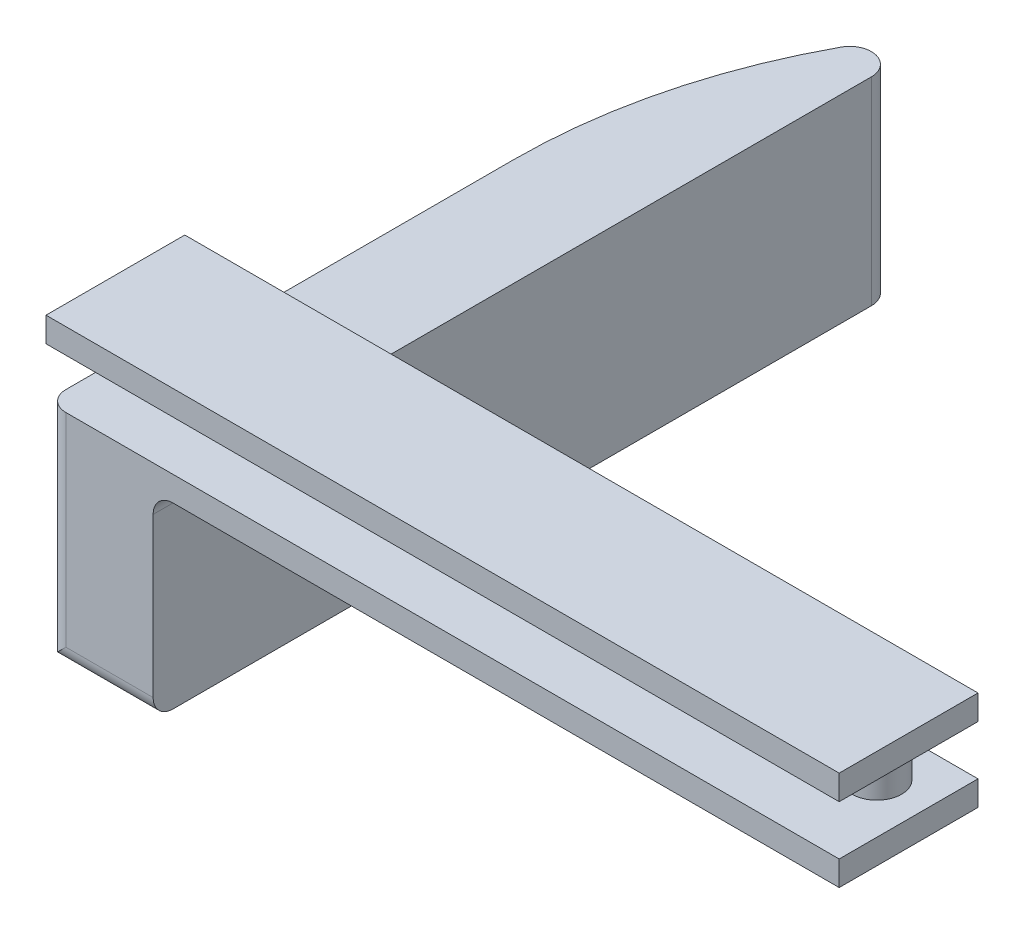
SolidWorks part; units mm, degrees
ref_plane "Front Plane" through (0, 0, 0) normal (0, 0, 1) x (1, 0, 0)
ref_plane "Top Plane" through (0, 0, 0) normal (0, 1, 0) x (1, 0, 0)
ref_plane "Right Plane" through (0, 0, 0) normal (1, 0, 0) x (0, 0, -1)
sketch "Sketch2" plane through (0, 0, 0) normal (0, 1, 0) x (1, 0, 0)
  line L1 (0, 0) -> (101.6, 0)
  line L2 (0, 0) -> (0, 17.78)
  line L3 (0, 17.78) -> (101.6, 17.78)
  line L4 (101.6, 0) -> (101.6, 17.78)
  dimension "D1" = 17.78
  dimension "D2" = 101.6
extrude "Boss-Extrude1" add sketch "Sketch2" along normal blind 3.175
sketch "Sketch3" plane through (0, 0, 0) normal (0, -1, 0) x (1, 0, 0)
  line L0 (95.25, -11.176) -> (6.35, -11.176) construction
  line L1 (95.25, -14.351) -> (6.35, -14.351)
  line L2 (95.25, -8.001) -> (6.35, -8.001)
  line L3 (0, 0) -> (101.6, 0) construction
  line L4 (0, -17.78) -> (0, 0) construction
  arc A0 (95.25, -14.351) -> (95.25, -8.001) centre (95.25, -11.176) ccw
  arc A1 (6.35, -8.001) -> (6.35, -14.351) centre (6.35, -11.176) ccw
  point P2 (50.8, -11.176)
  dimension "D1" = 88.9
  dimension "D2" = 11.176
  dimension "D3" = 6.35
  dimension "D4" = 6.35
extrude "Boss-Extrude2" add sketch "Sketch3" along normal blind 6.35 contours L2 A1 L1 A0
ref_plane "Plane1" through (0, -3.175, 0) normal (0, -1, 0) x (-1, 0, 0)
mirror "Mirror1" about plane through (0, -3.175, 0) normal (0, -1, 0) of "Boss-Extrude1"
sketch "Sketch5" plane through (0, -9.525, 0) normal (0, -1, 0) x (1, 0, 0)
  line L31 (0, 0) -> (13.7244, 0)
  line L32 (0, 0) -> (0, -59.8993)
  line L36 (13.7244, 0) -> (13.7244, -101.6)
  arc A2 (0, -59.8993) -> (13.7244, -101.6) centre (70.2144, -59.8993) ccw
  dimension "D1" = 101.6
extrude "Boss-Extrude3" add sketch "Sketch5" along normal blind 25.4
fillet "Fillet2" radius 2.794 1 edges at (13.7244, -22.225, -101.6)
fillet "Fillet3" radius 2.54 3 edges at (13.7244, -9.525, -8.89) (0, -20.6375, 0) (6.8622, -34.925, 0)
